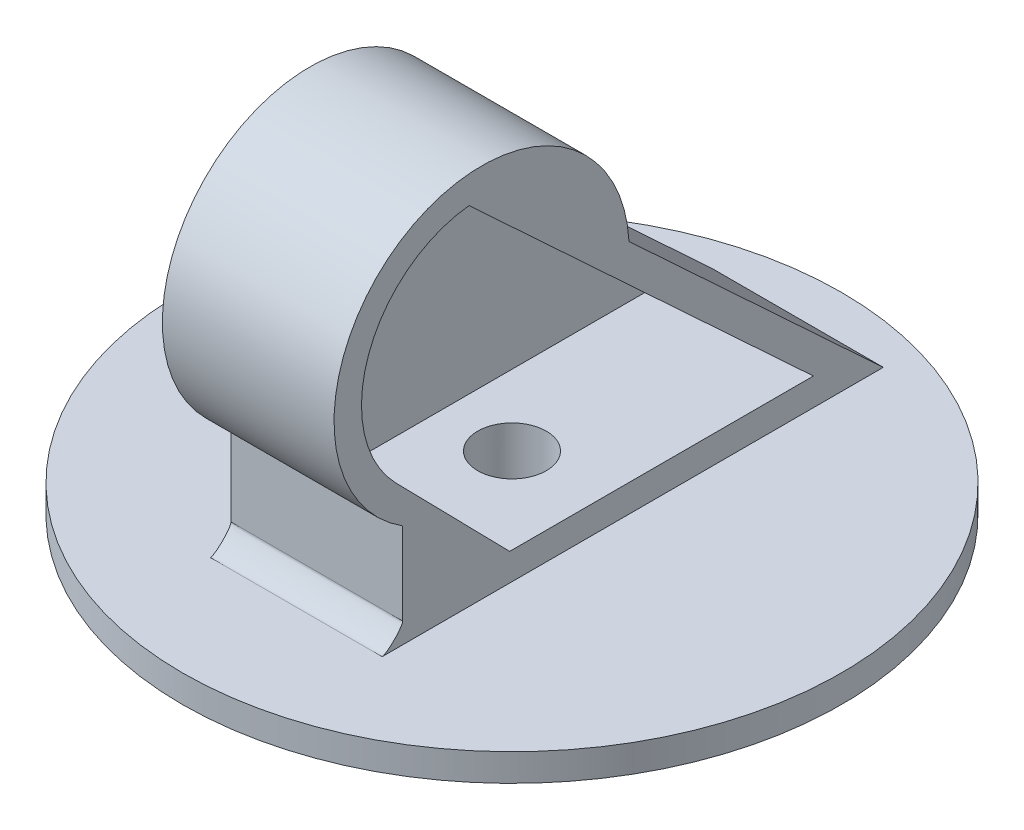
SolidWorks part; units mm, degrees
ref_plane "Alzado" through (0, 0, 0) normal (0, 0, 1) x (1, 0, 0)
ref_plane "Planta" through (0, 0, 0) normal (0, 1, 0) x (1, 0, 0)
ref_plane "Vista lateral" through (0, 0, 0) normal (1, 0, 0) x (0, 0, -1)
sketch "Croquis1" plane through (0, 0, 0) normal (0, 1, 0) x (1, 0, 0)
  line L0 (0, 0) -> (48, 0) construction
  line L1 (48, 0) -> (78, 0) construction
  line L2 (78, 0) -> (78, -48) construction
  line L4 (78, -48) -> (0, -48)
  line L5 (78, -48) -> (78, 48)
  line L6 (78, 48) -> (0, 48)
  line L7 (0, -48) -> (0, 48)
  circle A0 centre (0, 0) radius 48
sketch "Croquis3" plane through (0, 0, 0) normal (0, 1, 0) x (1, 0, 0)
  circle A0 centre (0, 140.8236) radius 48
extrude "Saliente-Extruir2" add sketch "Croquis3" along normal blind 4 separate body
sketch "Croquis5" plane through (0, 0, 0) normal (0, -1, 0) x (1, 0, 0)
  circle A0 centre (0, -140.8236) radius 43
  circle A1 centre (0, -140.8236) radius 39.5
  circle A3 centre (0, -99.5736) radius 1.75
extrude "Cortar-Extruir3" cut sketch "Croquis5" against normal blind 1.1 contours A3 region at (0, 0, -99.5736)
fillet "Redondeo3" radius 1.1 1 edges at (0, 1.1, -101.3236) type face fillet first side face at (0, 1.1, -101.3236) second side face at (0, 1.1, -101.3236)
pattern_circular "MatrizC5" count 8 over 360 about axis through (0, 0, -140.8236) along (0, 1, 0) of "Redondeo3", "Cortar-Extruir3"
sketch "Croquis6" plane through (0, 0, 0) normal (1, 0, 0) x (0, 0, -1)
  line L0 (182.4064, 4) -> (112.4064, 4)
  line L1 (188.8236, 4) -> (92.8236, 4) construction
  line L2 (112.4064, 4) -> (112.4064, 19)
  line L5 (182.4064, 4) -> (123.5307, 58.6658) construction
  line L6 (182.4064, 4) -> (145.3667, 38.3912)
  line L7 (145.3667, 38.3912) -> (112.4064, 19)
  circle A0 centre (123.9014, 37.169) radius 21.5
  dimension "D1" = 43
  dimension "D2" = 80.3411
  dimension "D3" = 15
  dimension "D4" = 70
extrude "Saliente-Extruir3" add sketch "Croquis6" along normal mid plane 25 contours L7 A0 | L7 A0 | A0 L2 L0 L6 | A0 region at (0, 13.9955, -145.9676) region at (0, 24.5613, -131.3188) region at (0, 40.7124, -121.8168)
fillet "Redondeo4" radius 3 1 edges at (0, 4, -112.4064) type face fillet first side face at (0, 11.5, -112.4064) second side face at (0, 4, -147.4064) conic radius 10
sketch "Croquis7" plane through (12.5, 0, 0) normal (1, 0, 0) x (0, 0, -1)
  line L0 (141.3929, 36.6225) -> (122.0611, 54.572) construction
  line L1 (111.4035, 24.9195) -> (127.9866, 8)
  line L2 (127.9866, 8) -> (172.2196, 8)
  line L4 (141.3929, 36.6225) -> (111.4035, 24.9195)
  line L8 (172.2196, 8) -> (141.3929, 36.6225)
  arc A0 (145.3667, 38.3912) -> (112.4064, 19) centre (123.9014, 37.169) ccw construction
  circle A1 centre (123.9014, 37.169) radius 17.5
  dimension "D1" = 4
extrude "Cortar-Extruir4" cut sketch "Croquis7" against normal blind 22.8 contours L4 L0 A1 | L4 A1 | A1 L1 L2 L8 region at (12.5, 39.5953, -120.5124) region at (12.5, 26.6836, -127.9932) region at (12.5, 17.1606, -143.9881)
sketch "Croquis8" plane through (0, 0, 0) normal (0, 1, 0) x (1, 0, 0)
  circle A0 centre (0, 140.8236) radius 5
extrude "Cortar-Extruir5" cut sketch "Croquis8" along normal blind 14.8
